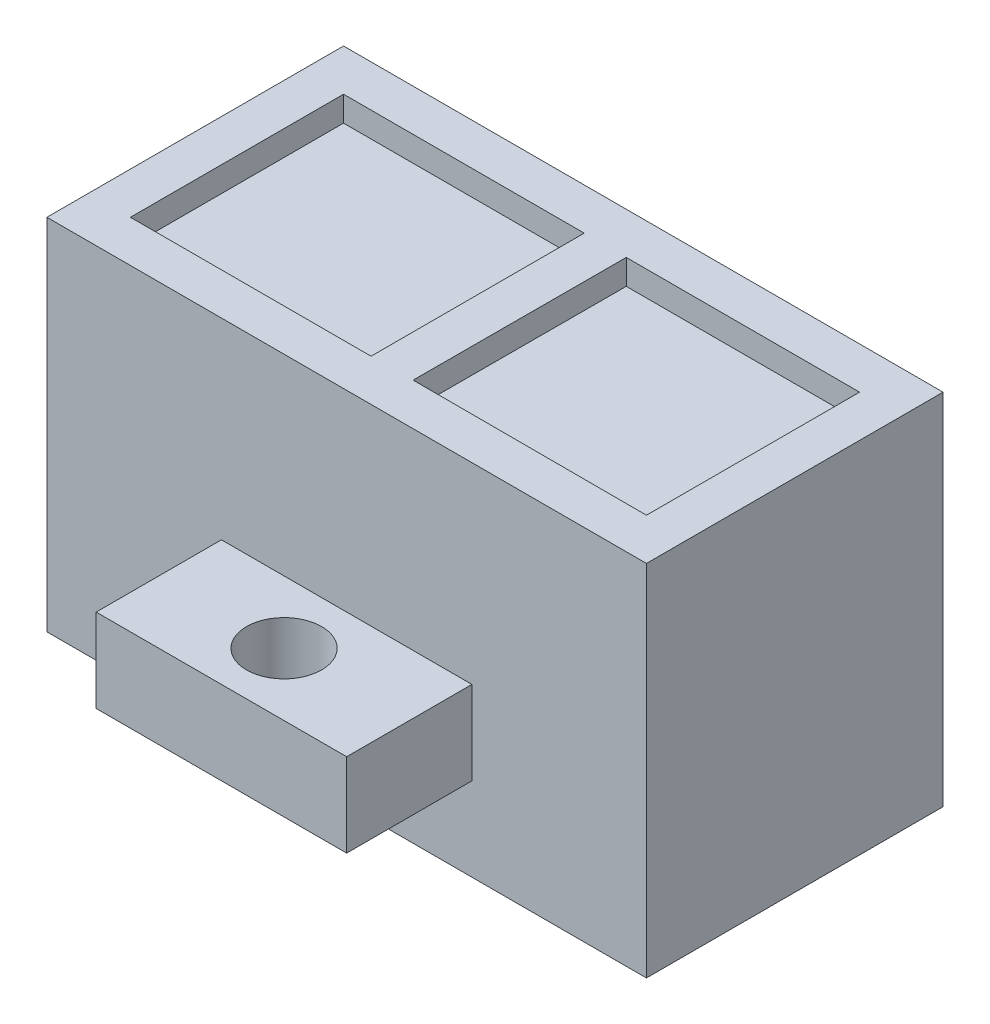
SolidWorks part; units mm, degrees
ref_plane "前视基准面" through (0, 0, 0) normal (0, 0, 1) x (1, 0, 0)
ref_plane "上视基准面" through (0, 0, 0) normal (0, 1, 0) x (1, 0, 0)
ref_plane "右视基准面" through (0, 0, 0) normal (1, 0, 0) x (0, 0, -1)
other "Configuration Table"
sketch "草图1" plane through (0, 0, 0) normal (0, 1, 0) x (1, 0, 0)
  line L0 (15, 7.5) -> (35.902, 7.5)
  line L1 (-15, -7.5) -> (15, -7.5)
  line L2 (-15, -7.5) -> (-15, 7.5)
  line L4 (15, -7.5) -> (15, 7.5)
  line L5 (-15, -7.5) -> (15, 7.5) construction
  line L6 (-15, 7.5) -> (15, -7.5) construction
  line L7 (-35.902, 43.0062) -> (35.902, 43.0062)
  line L8 (-35.902, 43.0062) -> (-35.902, 7.5)
  line L9 (-35.902, 7.5) -> (-15, 7.5)
  line L10 (35.902, 43.0062) -> (35.902, 7.5)
  line L11 (-35.902, 43.0062) -> (35.902, 7.5) construction
  line L12 (-35.902, 7.5) -> (35.902, 43.0062) construction
  circle A0 centre (0, 0) radius 4.5
  point P7 (0, 25.2531)
  dimension "D1" = 9
  dimension "D2" = 30
  dimension "D3" = 15
extrude "凸台-拉伸1" add sketch "草图1" along normal blind 10
sketch "草图2" plane through (0, 10, 0) normal (0, 1, 0) x (1, 0, 0)
  line L0 (-35.902, 7.5) -> (35.902, 7.5)
  line L1 (-35.902, 7.5) -> (-35.902, 43.0281)
  line L2 (35.902, 7.5) -> (35.902, 43.0281)
  line L3 (-35.902, 43.0281) -> (35.902, 43.0281)
extrude "凸台-拉伸2" add sketch "草图2" along normal blind 20 and the other way blind 20
sketch "草图3" plane through (0, 30, 0) normal (0, 1, 0) x (1, 0, 0)
  line L0 (30.902, 38.0281) -> (2.9566, 38.0281)
  line L1 (-30.902, 38.0281) -> (-30.902, 12.5)
  line L2 (-30.902, 12.5) -> (-2.0808, 12.5)
  line L3 (30.902, 12.5) -> (30.902, 38.0281)
  line L4 (-35.902, 43.0281) -> (-35.902, 7.5)
  line L5 (-35.902, 7.5) -> (35.902, 7.5)
  line L6 (35.902, 7.5) -> (35.902, 43.0281)
  line L7 (35.902, 43.0281) -> (-35.902, 43.0281)
  line L8 (-35.902, 43.0281) -> (-35.902, 7.5)
  line L9 (-35.902, 7.5) -> (35.902, 7.5)
  line L10 (35.902, 7.5) -> (35.902, 43.0281)
  line L11 (35.902, 43.0281) -> (-35.902, 43.0281)
  line L12 (-30.902, 38.0281) -> (-2.0808, 38.0281)
  line L13 (-2.0808, 38.0281) -> (-2.0808, 12.4589)
  line L14 (2.9567, 38.0726) -> (2.9192, 12.5411)
  line L15 (30.902, 38.0281) -> (-30.902, 38.0281) construction
  line L16 (-30.902, 12.5) -> (30.902, 12.5) construction
  line L17 (2.9192, 12.5411) -> (30.902, 12.5)
  point P14 (-2.0808, 38.0471)
  line M12 (-35.902, 43.0281) -> (-35.902, 7.5)
  line M13 (-35.902, 7.5) -> (35.902, 7.5)
  line M14 (35.902, 7.5) -> (35.902, 43.0281)
  line M15 (35.902, 43.0281) -> (-35.902, 43.0281)
  dimension "D1" = 0
  dimension "D2" = 5
extrude "凸台-拉伸3" add sketch "草图3" along normal blind 3 contours L17 L14 L0 L3 L12 L13 L2 L1 M15 M12 M13 M14 region at (0.0562, 30, -25.2593)
